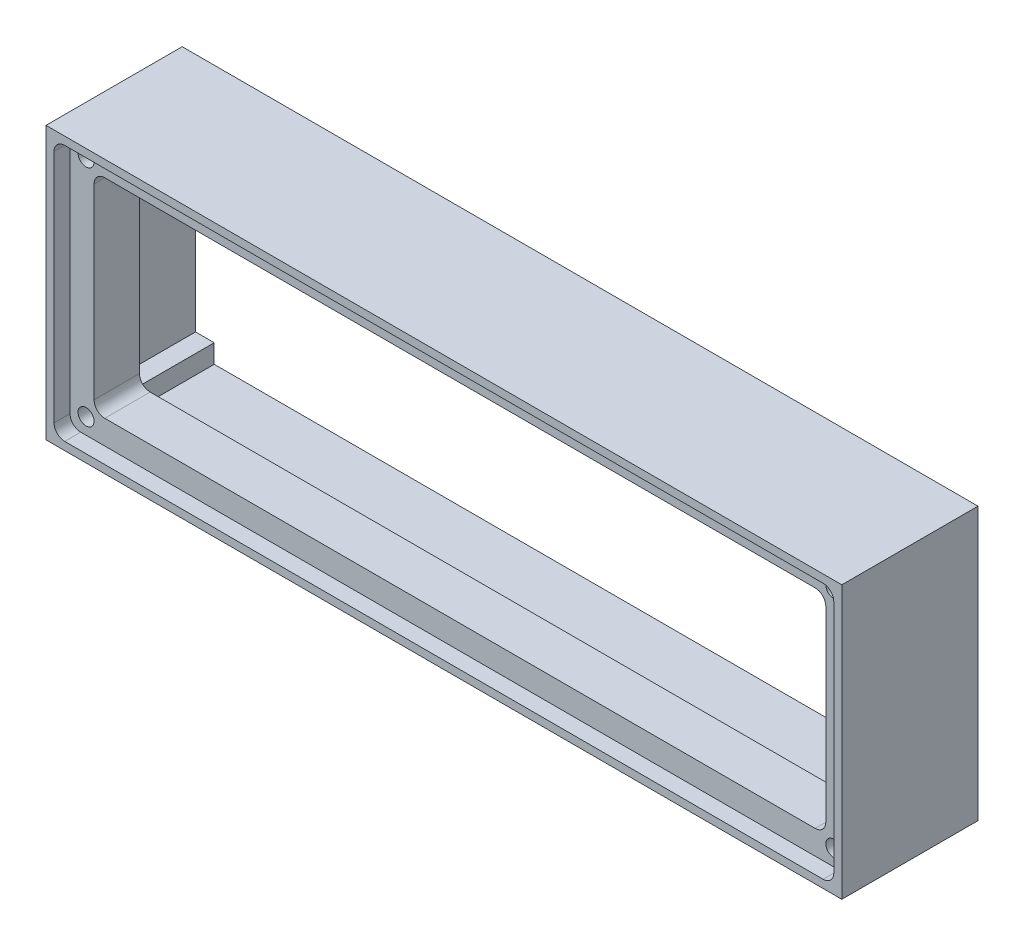
SolidWorks part; units mm, degrees
ref_plane "Front Plane" through (0, 0, 0) normal (0, 0, 1) x (1, 0, 0)
ref_plane "Top Plane" through (0, 0, 0) normal (0, 1, 0) x (1, 0, 0)
ref_plane "Right Plane" through (0, 0, 0) normal (1, 0, 0) x (0, 0, -1)
sketch "Sketch1" plane through (0, 0, 0) normal (0, 0, 1) x (1, 0, 0)
  line L1 (0, 0) -> (149, 0)
  line L2 (0, 0) -> (0, 51)
  line L3 (0, 51) -> (149, 51)
  line L4 (149, 0) -> (149, 51)
  dimension "D1" = 149
  dimension "D2" = 51
extrude "Extrude-Thin1" add sketch "Sketch1" along normal blind 25.5 thin thin type one direction reverse wall 6
sketch "Sketch2" plane through (0, 0, 25.5) normal (0, 0, 1) x (1, 0, 0)
  line L8 (1.5, 49.5) -> (1.5, 1.5)
  line L9 (1.5, 1.5) -> (147.5, 1.5)
  line L10 (147.5, 1.5) -> (147.5, 49.5)
  line L11 (147.5, 49.5) -> (1.5, 49.5)
  line L12 (1.5, 49.5) -> (1.5, 1.5)
  line L13 (1.5, 1.5) -> (147.5, 1.5)
  line L14 (147.5, 1.5) -> (147.5, 49.5)
  line L15 (147.5, 49.5) -> (1.5, 49.5)
  dimension "D1" = 1.5
extrude "Cut-Extrude1" cut sketch "Sketch2" against normal blind 3 contours L12 L13 L14 L15
sketch "Sketch3" plane through (0, 0, 22.5) normal (0, 0, 1) x (1, 0, 0)
  line L8 (144.5, 46.5) -> (4.5, 46.5)
  line L9 (4.5, 46.5) -> (4.5, 4.5)
  line L10 (4.5, 4.5) -> (144.5, 4.5)
  line L11 (144.5, 4.5) -> (144.5, 46.5)
  line L12 (144.5, 46.5) -> (4.5, 46.5)
  line L13 (4.5, 46.5) -> (4.5, 4.5)
  line L14 (4.5, 4.5) -> (144.5, 4.5)
  line L15 (144.5, 4.5) -> (144.5, 46.5)
  circle A0 centre (4.5, 46.5) radius 1.5
  circle A1 centre (4.5, 4.5) radius 1.5
  circle A3 centre (144.5, 4.5) radius 1.5
  circle A4 centre (144.5, 46.5) radius 1.5
  dimension "D2" = 3
  dimension "D1" = 3
extrude "Cut-Extrude2" cut sketch "Sketch3" against normal blind 8 contours L12 A0 L13 | L13 A0 L12 | L14 A1 L13 | L13 A1 L14 | L15 A4 L12 | L12 A4 L15 | L14 A3 L15 | L15 A3 L14 region at (5.1366, 45.8634, 22.5) region at (4.2878, 46.7122, 22.5) region at (144.7122, 46.7122, 22.5) region at (143.8634, 45.8634, 22.5) region at (5.1366, 5.1366, 22.5) region at (4.2878, 4.2878, 22.5) region at (144.7122, 4.2878, 22.5) region at (143.8634, 5.1366, 22.5)
sketch "Sketch4" plane through (0, 0, 0) normal (0, 0, -1) x (-1, 0, 0)
  line L8 (-3, 3) -> (-3, 48)
  line L9 (-3, 48) -> (-146, 48)
  line L10 (-146, 48) -> (-146, 3)
  line L11 (-146, 3) -> (-3, 3)
  line L12 (-3, 3) -> (-3, 48)
  line L13 (-3, 48) -> (-146, 48)
  line L14 (-146, 48) -> (-146, 3)
  line L15 (-146, 3) -> (-3, 3)
  circle A0 centre (-146, 48) radius 1.5
  circle A1 centre (-3, 48) radius 1.5
  circle A2 centre (-3, 3) radius 1.5
  circle A3 centre (-146, 3) radius 1.5
  dimension "D2" = 3
  dimension "D1" = 3
extrude "Cut-Extrude3" cut sketch "Sketch4" against normal blind 8 contours L13 A0 L14 | L14 A3 L15 | L15 A3 L14 | L14 A0 L13 | L13 A1 L12 | L12 A1 L13 | L15 A2 L12 | L12 A2 L15 region at (3.6366, 3.6366, 0) region at (2.7878, 2.7878, 0) region at (3.6366, 47.3634, 0) region at (2.7878, 48.2122, 0) region at (146.2122, 2.7878, 0) region at (145.3634, 3.6366, 0) region at (145.3634, 47.3634, 0) region at (146.2122, 48.2122, 0)
sketch "Sketch6" plane through (0, 0, 0) normal (0, 0, -1) x (-1, 0, 0)
  line L0 (-143, 45) -> (-146.5, 45)
  line L1 (-143, 6) -> (-146.5, 6)
  line L2 (-146.5, 6) -> (-146.5, 45)
  line L3 (-74.5, 51) -> (-74.5, 0) construction
  line L4 (-149, 51) -> (0, 51) construction
  line L5 (0, 0) -> (-149, 0) construction
  line L6 (-143, 45) -> (-143, 48.5)
  line L7 (-143, 48.5) -> (-6, 48.5)
  line L8 (-143, 6) -> (-143, 2.5)
  line L9 (-143, 2.5) -> (-6, 2.5)
  line L10 (-6, 6) -> (-6, 2.5)
  line L11 (-6, 6) -> (-2.5, 6)
  line L12 (-2.5, 6) -> (-2.5, 45)
  line L13 (-6, 45) -> (-2.5, 45)
  line L14 (-6, 45) -> (-6, 48.5)
  point P17 (-74.5, 2.5)
  point P22 (-74.5, 48.5)
  dimension "D1" = 3.5
fillet "Fillet1" radius 2 4 edges at (147.5, 1.5, 24) (147.5, 49.5, 24) (1.5, 49.5, 24) (1.5, 1.5, 24)
fillet "Fillet2" radius 2 4 edges at (143, 45, 11.25) (143, 6, 11.25) (6, 6, 11.25) (6, 45, 11.25)
extrude "Cut-Extrude7" cut sketch "Sketch6" against normal blind 14 contours L9 L10 L11 L12 L13 L14 L7 L6 L0 L2 L1 L8
